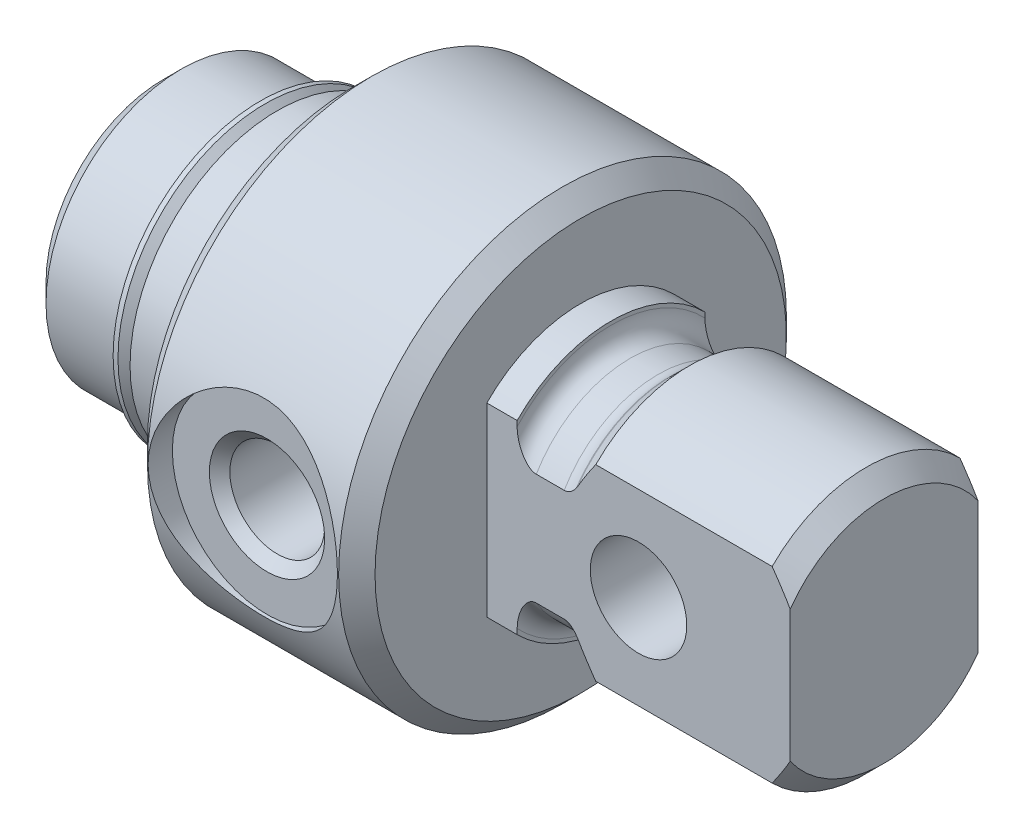
SolidWorks part; units mm, degrees
material "AISI 304"
ref_plane "Front Plane" through (0, 0, 0) normal (0, 0, 1) x (1, 0, 0)
ref_plane "Top Plane" through (0, 0, 0) normal (0, 1, 0) x (1, 0, 0)
ref_plane "Right Plane" through (0, 0, 0) normal (1, 0, 0) x (0, 0, -1)
ref_plane "Plane1" through (30.1752, 0, 0) normal (1, 0, 0) x (0, 0, -1)
sketch "Sketch1" plane through (0, 0, 0) normal (0, 0, 1) x (1, 0, 0)
  line L0 (0, 0) -> (0, 4.9085)
  line L1 (0, 4.9085) -> (0.762, 5.6706)
  line L2 (0.762, 5.6706) -> (3.7592, 5.6706)
  line L3 (3.7592, 5.6706) -> (4.2672, 5.1626)
  line L4 (4.2672, 5.1626) -> (4.7752, 5.1626)
  line L5 (4.7752, 5.1626) -> (4.7752, 6.1658)
  line L6 (4.7752, 6.1658) -> (7.9502, 6.1658)
  line L7 (7.9502, 6.1658) -> (7.9502, 8.6106)
  line L8 (7.9502, 8.6106) -> (8.7122, 9.3726)
  line L9 (8.7122, 9.3726) -> (16.7132, 9.3726)
  line L10 (16.7132, 9.3726) -> (17.4752, 8.6106)
  line L11 (17.4752, 8.6106) -> (17.4752, 0)
  line L12 (17.4752, 0) -> (0, 0)
  line L13 (17.4752, 0) -> (0, 0) construction
revolve "Revolve1" add sketch "Sketch1" angle 360 about L13 reverse direction yes
sketch "Sketch2" plane through (0, 0, 0) normal (0, 0, 1) x (1, 0, 0)
  line L0 (17.4752, 0) -> (17.4752, 5.5245)
  line L1 (17.4752, 5.5245) -> (18.7452, 5.5245)
  line L2 (18.7452, 5.5245) -> (18.7452, 5.3721)
  line L3 (19.5453, 4.572) -> (20.7137, 4.572)
  line L4 (21.2166, 4.7498) -> (21.2795, 4.8006)
  line L5 (21.2795, 4.8006) -> (22.0351, 5.5563)
  line L6 (22.0351, 5.5563) -> (29.4196, 5.5563)
  line L7 (29.4196, 5.5563) -> (30.1752, 4.8006)
  line L8 (30.1752, 4.8006) -> (30.1752, 0)
  line L9 (30.1752, 0) -> (17.4752, 0)
  line L10 (30.1752, 0) -> (17.4752, 0) construction
  arc A0 (18.7452, 5.3721) -> (19.5453, 4.572) centre (19.5453, 5.3721) ccw
  arc A1 (20.7137, 4.572) -> (21.2166, 4.7498) centre (20.7137, 5.3721) ccw
revolve "Revolve2" add sketch "Sketch2" angle 360 about L10 reverse direction yes
cosmetic thread "Cosmetic Thread1" parameters "D1"=8.8957, "D2"=9.6012
sketch "Sketch3" plane through (30.1752, 0, 0) normal (1, 0, 0) x (0, 0, -1)
  line L0 (-18.7452, -37.4904) -> (18.7452, -37.4904)
  line L1 (18.7452, -37.4904) -> (18.7452, 37.4904)
  line L2 (18.7452, 37.4904) -> (-18.7452, 37.4904)
  line L3 (-18.7452, 37.4904) -> (-18.7452, -37.4904)
  line L4 (-3.9306, -18.7452) -> (3.9306, -18.7452)
  line L5 (3.9306, -18.7452) -> (3.9306, 18.7452)
  line L6 (3.9306, 18.7452) -> (-3.9306, 18.7452)
  line L7 (-3.9306, 18.7452) -> (-3.9306, -18.7452)
extrude "Cut-Extrude1" cut sketch "Sketch3" against normal blind 12.7
ref_plane "Plane2" through (17.4752, 0, 0) normal (1, 0, 0) x (0, 0, -1)
hole_wizard "Hole1" positions "Sketch5" profile "Sketch4" legacy
sketch "Sketch5" plane through (0, 0, 0) normal (-1, 0, 0) x (0, 0, 1)
  point P0 (0, 0)
sketch "Sketch4" plane through (0, 0, 0) normal (0, 1, 0) x (0, 0, 1)
  line L0 (0, 0) -> (0, 18.8373)
  line L1 (0, 18.8373) -> (2.3812, 17.4625)
  line L2 (2.3812, 17.4625) -> (2.3812, 0)
  line L4 (2.3812, 0) -> (0, 0)
  line L6 (0, 18.8373) -> (-2.3812, 17.4625) construction
  line L7 (0, -4.2442) -> (0, 117.3081) construction
  dimension "Diameter" = 4.7625
  dimension "Depth" = 17.4625
  dimension "Drill Angle" = 120
ref_plane "Plane3" through (0, 0, 0) normal (0, 0.9998, 0.0175) x (1, 0, 0)
sketch "Sketch6" plane through (0, 0, 0) normal (0, 1, 0) x (1, 0, 0)
  line L0 (12.7, 0) -> (14.6837, 0)
  line L1 (14.6837, 0) -> (14.6837, -7.9273)
  line L2 (14.6837, -7.9273) -> (15.113, -8.3566)
  line L3 (15.113, -8.3566) -> (16.6624, -8.3566)
  line L4 (16.6624, -8.3566) -> (16.6624, -9.3726)
  line L5 (16.6624, -9.3726) -> (12.7, -9.3726)
  line L6 (12.7, -9.3726) -> (12.7, 0)
  line L7 (12.7, -9.3726) -> (12.7, 0) construction
revolve "Cut-Revolve1" cut sketch "Sketch6" angle 360 about L7 reverse direction yes
cosmetic thread "Cosmetic Thread2" parameters "D1"=5.9753, "D2"=4.826
ref_plane "Plane4" through (12.7, 0, 0) normal (1, 0, 0) x (0, 0, -1)
ref_plane "Plane5" through (4.2672, 0, 0) normal (1, 0, 0) x (0, 0, -1)
sketch "Sketch7" plane through (0, 0, 0) normal (0, 0, 1) x (1, 0, 0)
  line L0 (4.0665, 6.0817) -> (4.6636, 5.4846)
  line L1 (4.6636, 5.305) -> (4.5212, 5.1625)
  line L2 (4.5212, 5.1625) -> (4.2672, 5.1625)
  line L3 (4.2672, 5.1625) -> (4.2672, 4.9085)
  line L4 (4.2672, 4.9085) -> (4.7752, 4.9085)
  line L5 (4.7752, 4.9085) -> (4.7752, 5.6603)
  line L6 (4.7752, 5.6603) -> (4.2697, 6.1658)
  line L7 (4.2697, 6.1658) -> (4.0665, 6.1658)
  line L8 (4.0665, 6.1658) -> (4.0665, 6.0817)
  line L9 (4.7752, 0) -> (4.2672, 0) construction
  arc A0 (4.6636, 5.4846) -> (4.6636, 5.305) centre (4.5738, 5.3948) cw
revolve "Revolve3" add sketch "Sketch7" angle 360 about L9 reverse direction yes
ref_plane "Plane6" through (30.3022, 0, 0) normal (1, 0, 0) x (0, 0, -1)
sketch "Sketch8" plane through (0, 0, 0) normal (0, 0, 1) x (1, 0, 0)
  circle A0 centre (23.8252, 0) radius 2.0193
extrude "Cut-Extrude2" cut sketch "Sketch8" along normal blind 5.896 and the other way blind 5.896
ref_plane "Plane7" through (18.7452, 0, 0) normal (1, 0, 0) x (0, 0, -1)
ref_plane "Plane8" through (25.4, 0, 0) normal (1, 0, 0) x (0, 0, -1)
ref_plane "Plane9" through (23.8252, 0, 0) normal (1, 0, 0) x (0, 0, -1)
ref_plane "Plane10" through (30.1752, 0, 0) normal (1, 0, 0) x (0, 0, -1)
ref_plane "Plane11" through (0, 0, 0) normal (0, 0, 1) x (1, 0, 0)
ref_plane "Plane12" through (18.7452, 0, 0) normal (1, 0, 0) x (0, 0, -1)
ref_plane "Plane13" through (0, 0, 0) normal (0, 1, 0) x (1, 0, 0)
ref_plane "Plane14" through (0, 0, 0) normal (0, 1, 0) x (1, 0, 0)
ref_plane "Plane15" through (17.4752, 0, 0) normal (1, 0, 0) x (0, 0, -1)
ref_plane "1 XY" through (18.7452, 0, 0) normal (1, 0, 0) x (0, 0, -1)
ref_plane "1 XZ" through (0, 0, 0) normal (0, -1, 0) x (-1, 0, 0)
ref_plane "1 YZ" through (0, 0, 0) normal (0, 0, -1) x (-1, 0, 0)
ref_axis "1 X" through (18.7452, 0, 80.9) along (0, 0, -1)
ref_axis "1 Y" through (18.7452, -50, 0) along (0, 1, 0)
ref_axis "1 Z" through (80.9, 0, 0) along (-1, 0, 0)
sketch3d "1"
  point P0 (18.7452, 0, 0)
ref_plane "c1 XY" through (0, 0, 0) normal (0, 0, 1) x (1, 0, 0)
ref_plane "c1 XZ" through (0, 5.5245, 0) normal (0, -1, 0) x (-1, 0, 0)
ref_plane "c1 YZ" through (17.4752, 0, 0) normal (1, 0, 0) x (0, 0, -1)
ref_axis "c1 X" through (-80.9, 5.5245, 0) along (1, 0, 0)
ref_axis "c1 Y" through (17.4752, -50, 0) along (0, 1, 0)
ref_axis "c1 Z" through (17.4752, 5.5245, 80.9) along (0, 0, -1)
sketch3d "c1"
  point P0 (17.4752, 5.5245, 0)
ref_plane "c2 XY" through (0, 0, 0) normal (0, 0, 1) x (1, 0, 0)
ref_plane "c2 XZ" through (0, -5.5245, 0) normal (0, -1, 0) x (-1, 0, 0)
ref_plane "c2 YZ" through (17.4752, 0, 0) normal (1, 0, 0) x (0, 0, -1)
ref_axis "c2 X" through (-80.9, -5.5245, 0) along (1, 0, 0)
ref_axis "c2 Y" through (17.4752, -50, 0) along (0, 1, 0)
ref_axis "c2 Z" through (17.4752, -5.5245, 80.9) along (0, 0, -1)
sketch3d "c2"
  point P0 (17.4752, -5.5245, 0)
ref_plane "cc1 XY" through (0, 0, 0) normal (0, 0, 1) x (1, 0, 0)
ref_plane "cc1 XZ" through (0, 0, 0) normal (0, -1, 0) x (-1, 0, 0)
ref_plane "cc1 YZ" through (17.4752, 0, 0) normal (1, 0, 0) x (0, 0, -1)
ref_axis "cc1 X" through (-80.9, 0, 0) along (1, 0, 0)
ref_axis "cc1 Y" through (17.4752, -50, 0) along (0, 1, 0)
ref_axis "cc1 Z" through (17.4752, 0, 80.9) along (0, 0, -1)
sketch3d "cc1"
  point P0 (17.4752, 0, 0)
ref_plane "cc2 XY" through (0, 0, 0) normal (0, 0, 1) x (1, 0, 0)
ref_plane "cc2 XZ" through (0, 0, 0) normal (0, -1, 0) x (-1, 0, 0)
ref_plane "cc2 YZ" through (18.7452, 0, 0) normal (1, 0, 0) x (0, 0, -1)
ref_axis "cc2 X" through (-80.9, 0, 0) along (1, 0, 0)
ref_axis "cc2 Y" through (18.7452, -50, 0) along (0, 1, 0)
ref_axis "cc2 Z" through (18.7452, 0, 80.9) along (0, 0, -1)
sketch3d "cc2"
  point P0 (18.7452, 0, 0)
ref_plane "lovra1 XY" through (25.4, 0, 0) normal (1, 0, 0) x (0, 0, -1)
ref_plane "lovra1 XZ" through (0, 0, 0) normal (0, -1, 0) x (-1, 0, 0)
ref_plane "lovra1 YZ" through (0, 0, 0) normal (0, 0, -1) x (-1, 0, 0)
ref_axis "lovra1 X" through (25.4, 0, 80.9) along (0, 0, -1)
ref_axis "lovra1 Y" through (25.4, -50, 0) along (0, 1, 0)
ref_axis "lovra1 Z" through (80.9, 0, 0) along (-1, 0, 0)
sketch3d "lovra1"
  point P0 (25.4, 0, 0)
ref_plane "lovra2 XY" through (25.4, 0, 0) normal (1, 0, 0) x (0, 0, -1)
ref_plane "lovra2 XZ" through (0, 4.699, 0) normal (0, -1, 0) x (-1, 0, 0)
ref_plane "lovra2 YZ" through (0, 0, 0) normal (0, 0, -1) x (-1, 0, 0)
ref_axis "lovra2 X" through (25.4, 4.699, 80.9) along (0, 0, -1)
ref_axis "lovra2 Y" through (25.4, -50, 0) along (0, 1, 0)
ref_axis "lovra2 Z" through (80.9, 4.699, 0) along (-1, 0, 0)
sketch3d "lovra2"
  point P0 (25.4, 4.699, 0)
ref_plane "lovra21 XY" through (0, 0, 0) normal (1, 0, 0) x (0, 0, -1)
ref_plane "lovra21 XZ" through (0, 0, 0) normal (0, -1, 0) x (-1, 0, 0)
ref_plane "lovra21 YZ" through (0, 0, 5.2705) normal (0, 0, -1) x (-1, 0, 0)
ref_axis "lovra21 X" through (0, 0, 80.9) along (0, 0, -1)
ref_axis "lovra21 Y" through (0, -50, 5.2705) along (0, 1, 0)
ref_axis "lovra21 Z" through (80.9, 0, 5.2705) along (-1, 0, 0)
sketch3d "lovra21"
  point P0 (0, 0, 5.2705)
ref_plane "lovra22 XY" through (0, 0, 0) normal (1, 0, 0) x (0, 0, -1)
ref_plane "lovra22 XZ" through (0, 0, 0) normal (0, -1, 0) x (-1, 0, 0)
ref_plane "lovra22 YZ" through (0, 0, -5.2705) normal (0, 0, -1) x (-1, 0, 0)
ref_axis "lovra22 X" through (0, 0, 80.9) along (0, 0, -1)
ref_axis "lovra22 Y" through (0, -50, -5.2705) along (0, 1, 0)
ref_axis "lovra22 Z" through (80.9, 0, -5.2705) along (-1, 0, 0)
sketch3d "lovra22"
  point P0 (0, 0, -5.2705)
ref_plane "lovra3 XY" through (25.4, 0, 0) normal (1, 0, 0) x (0, 0, -1)
ref_plane "lovra3 XZ" through (0, -4.699, 0) normal (0, -1, 0) x (-1, 0, 0)
ref_plane "lovra3 YZ" through (0, 0, 0) normal (0, 0, -1) x (-1, 0, 0)
ref_axis "lovra3 X" through (25.4, -4.699, 80.9) along (0, 0, -1)
ref_axis "lovra3 Y" through (25.4, -50, 0) along (0, 1, 0)
ref_axis "lovra3 Z" through (80.9, -4.699, 0) along (-1, 0, 0)
sketch3d "lovra3"
  point P0 (25.4, -4.699, 0)
ref_plane "olen XY" through (23.8252, 0, 0) normal (1, 0, 0) x (0, 0, -1)
ref_plane "olen XZ" through (0, 0, 0) normal (0, -1, 0) x (-1, 0, 0)
ref_plane "olen YZ" through (0, 0, 0) normal (0, 0, -1) x (-1, 0, 0)
ref_axis "olen X" through (23.8252, 0, 80.9) along (0, 0, -1)
ref_axis "olen Y" through (23.8252, -50, 0) along (0, 1, 0)
ref_axis "olen Z" through (80.9, 0, 0) along (-1, 0, 0)
sketch3d "olen"
  point P0 (23.8252, 0, 0)
ref_plane "p1 XY" through (30.1752, 0, 0) normal (1, 0, 0) x (0, 0, -1)
ref_plane "p1 XZ" through (0, 0, 0) normal (0, -1, 0) x (-1, 0, 0)
ref_plane "p1 YZ" through (0, 0, 3.9306) normal (0, 0, -1) x (-1, 0, 0)
ref_axis "p1 X" through (30.1752, 0, 80.9) along (0, 0, -1)
ref_axis "p1 Y" through (30.1752, -50, 3.9306) along (0, 1, 0)
ref_axis "p1 Z" through (80.9, 0, 3.9306) along (-1, 0, 0)
sketch3d "p1"
  point P0 (30.1752, 0, 3.9306)
ref_plane "p2 XY" through (30.1752, 0, 0) normal (1, 0, 0) x (0, 0, -1)
ref_plane "p2 XZ" through (0, 0, 0) normal (0, -1, 0) x (-1, 0, 0)
ref_plane "p2 YZ" through (0, 0, -3.9306) normal (0, 0, -1) x (-1, 0, 0)
ref_axis "p2 X" through (30.1752, 0, 80.9) along (0, 0, -1)
ref_axis "p2 Y" through (30.1752, -50, -3.9306) along (0, 1, 0)
ref_axis "p2 Z" through (80.9, 0, -3.9306) along (-1, 0, 0)
sketch3d "p2"
  point P0 (30.1752, 0, -3.9306)
ref_plane "port XY" through (0, 0, 0) normal (0, 0, 1) x (1, 0, 0)
ref_plane "port XZ" through (0, 0, 0) normal (0, -1, 0) x (-1, 0, 0)
ref_plane "port YZ" through (12.7, 0, 0) normal (1, 0, 0) x (0, 0, -1)
ref_axis "port X" through (-80.9, 0, 0) along (1, 0, 0)
ref_axis "port Y" through (12.7, -50, 0) along (0, 1, 0)
ref_axis "port Z" through (12.7, 0, 80.9) along (0, 0, -1)
sketch3d "port"
  point P0 (12.7, 0, 0)
ref_plane "port2 XY" through (30.1752, 0, 0) normal (1, 0, 0) x (0, 0, -1)
ref_plane "port2 XZ" through (0, 0, 0) normal (0, -1, 0) x (-1, 0, 0)
ref_plane "port2 YZ" through (0, 0, 0) normal (0, 0, -1) x (-1, 0, 0)
ref_axis "port2 X" through (30.1752, 0, 80.9) along (0, 0, -1)
ref_axis "port2 Y" through (30.1752, -50, 0) along (0, 1, 0)
ref_axis "port2 Z" through (80.9, 0, 0) along (-1, 0, 0)
sketch3d "port2"
  point P0 (30.1752, 0, 0)
ref_plane "thd1 XY" through (30.1752, 0, 0) normal (1, 0, 0) x (0, 0, -1)
ref_plane "thd1 XZ" through (0, 0, 0) normal (0, -1, 0) x (-1, 0, 0)
ref_plane "thd1 YZ" through (0, 0, 5.5563) normal (0, 0, -1) x (-1, 0, 0)
ref_axis "thd1 X" through (30.1752, 0, 80.9) along (0, 0, -1)
ref_axis "thd1 Y" through (30.1752, -50, 5.5563) along (0, 1, 0)
ref_axis "thd1 Z" through (80.9, 0, 5.5563) along (-1, 0, 0)
sketch3d "thd1"
  point P0 (30.1752, 0, 5.5563)
ref_plane "thd2 XY" through (30.1752, 0, 0) normal (1, 0, 0) x (0, 0, -1)
ref_plane "thd2 XZ" through (0, 0, 0) normal (0, -1, 0) x (-1, 0, 0)
ref_plane "thd2 YZ" through (0, 0, -5.5563) normal (0, 0, -1) x (-1, 0, 0)
ref_axis "thd2 X" through (30.1752, 0, 80.9) along (0, 0, -1)
ref_axis "thd2 Y" through (30.1752, -50, -5.5563) along (0, 1, 0)
ref_axis "thd2 Z" through (80.9, 0, -5.5563) along (-1, 0, 0)
sketch3d "thd2"
  point P0 (30.1752, 0, -5.5563)
ref_plane "to_mounting_bracket XY" through (17.4752, 0, 0) normal (1, 0, 0) x (0, 0, -1)
ref_plane "to_mounting_bracket XZ" through (0, 0, 0) normal (0, -1, 0) x (-1, 0, 0)
ref_plane "to_mounting_bracket YZ" through (0, 0, 0) normal (0, 0, -1) x (-1, 0, 0)
ref_axis "to_mounting_bracket X" through (17.4752, 0, 80.9) along (0, 0, -1)
ref_axis "to_mounting_bracket Y" through (17.4752, -50, 0) along (0, 1, 0)
ref_axis "to_mounting_bracket Z" through (80.9, 0, 0) along (-1, 0, 0)
sketch3d "to_mounting_bracket"
  point P0 (17.4752, 0, 0)
ref_plane "to_nut XY" through (18.7452, 0, 0) normal (1, 0, 0) x (0, 0, -1)
ref_plane "to_nut XZ" through (0, 0, 0) normal (0, -1, 0) x (-1, 0, 0)
ref_plane "to_nut YZ" through (0, 0, 0) normal (0, 0, -1) x (-1, 0, 0)
ref_axis "to_nut X" through (18.7452, 0, 80.9) along (0, 0, -1)
ref_axis "to_nut Y" through (18.7452, -50, 0) along (0, 1, 0)
ref_axis "to_nut Z" through (80.9, 0, 0) along (-1, 0, 0)
sketch3d "to_nut"
  point P0 (18.7452, 0, 0)
ref_plane "to_pin XY" through (0, 0, 0) normal (0, 0, 1) x (1, 0, 0)
ref_plane "to_pin XZ" through (0, 0, 0) normal (0, -1, 0) x (-1, 0, 0)
ref_plane "to_pin YZ" through (23.8252, 0, 0) normal (1, 0, 0) x (0, 0, -1)
ref_axis "to_pin X" through (-80.9, 0, 0) along (1, 0, 0)
ref_axis "to_pin Y" through (23.8252, -50, 0) along (0, 1, 0)
ref_axis "to_pin Z" through (23.8252, 0, 80.9) along (0, 0, -1)
sketch3d "to_pin"
  point P0 (23.8252, 0, 0)
ref_plane "to_screw XY" through (0, 0, 0) normal (0, 1, 0) x (1, 0, 0)
ref_plane "to_screw XZ" through (0, 0, 0) normal (0, 0, 1) x (1, 0, 0)
ref_plane "to_screw YZ" through (12.7, 0, 0) normal (1, 0, 0) x (0, 0, -1)
ref_axis "to_screw X" through (-80.9, 0, 0) along (1, 0, 0)
ref_axis "to_screw Y" through (12.7, 0, 50) along (0, 0, -1)
ref_axis "to_screw Z" through (12.7, 50, 0) along (0, -1, 0)
sketch3d "to_screw"
  point P0 (12.7, 0, 0)
ref_plane "to_tube XY" through (4.2672, 0, 0) normal (1, 0, 0) x (0, 0, -1)
ref_plane "to_tube XZ" through (0, 0, 0) normal (0, -1, 0) x (-1, 0, 0)
ref_plane "to_tube YZ" through (0, 0, 0) normal (0, 0, -1) x (-1, 0, 0)
ref_axis "to_tube X" through (4.2672, 0, 80.9) along (0, 0, -1)
ref_axis "to_tube Y" through (4.2672, -50, 0) along (0, 1, 0)
ref_axis "to_tube Z" through (80.9, 0, 0) along (-1, 0, 0)
sketch3d "to_tube"
  point P0 (4.2672, 0, 0)
